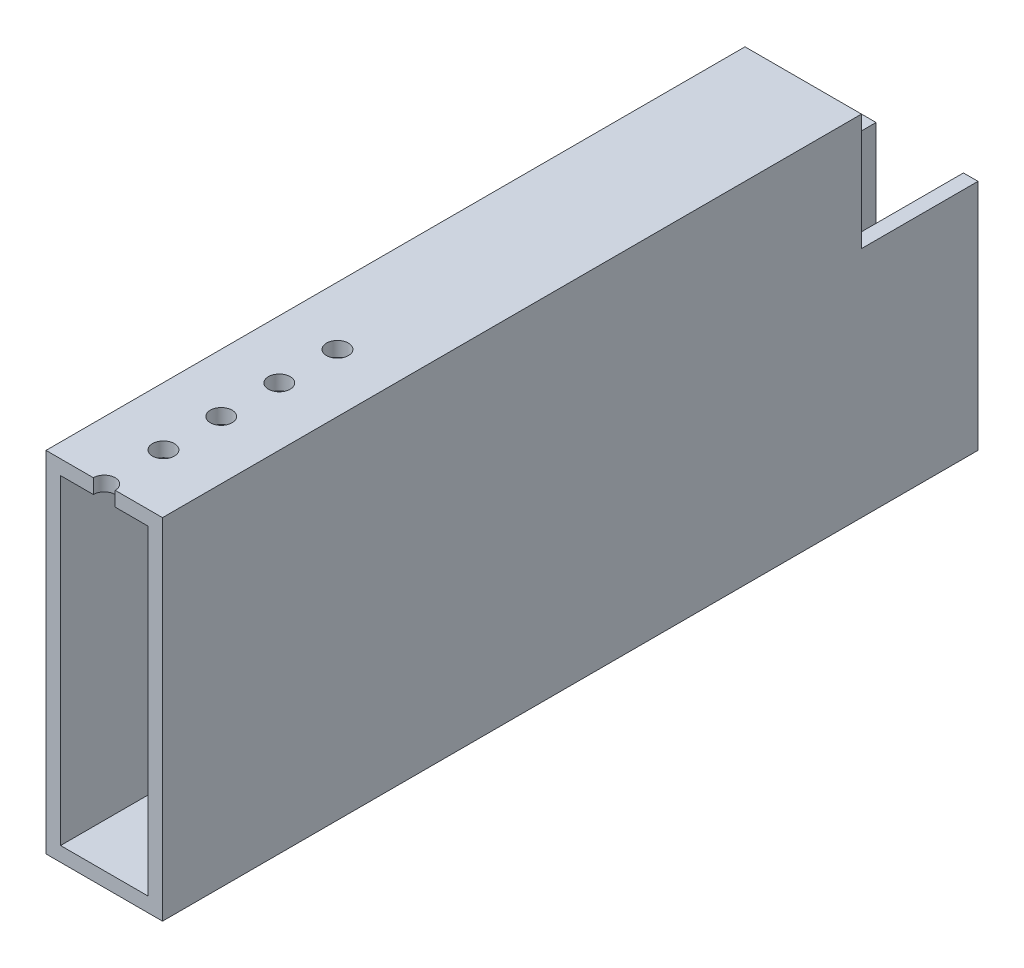
SolidWorks part; units mm, degrees
ref_plane "Front Plane" through (0, 0, 0) normal (0, 0, 1) x (1, 0, 0)
ref_plane "Top Plane" through (0, 0, 0) normal (0, 1, 0) x (1, 0, 0)
ref_plane "Right Plane" through (0, 0, 0) normal (1, 0, 0) x (0, 0, -1)
sketch "Sketch1" plane through (0, 0, 0) normal (0, 0, 1) x (1, 0, 0)
  line L1 (-12.7, -38.1) -> (12.7, -38.1)
  line L2 (-12.7, -38.1) -> (-12.7, 38.1)
  line L3 (-12.7, 38.1) -> (12.7, 38.1)
  line L4 (12.7, -38.1) -> (12.7, 38.1)
  line L5 (-12.7, -38.1) -> (12.7, 38.1) construction
  line L6 (-12.7, 38.1) -> (12.7, -38.1) construction
  point P0 (0, 0)
  dimension "D1" = 25.4
  dimension "D2" = 76.2
extrude "Boss-Extrude1" add sketch "Sketch1" along normal mid plane 177.8
shell "Shell1" thickness 3.175 removed face at (0, 0, -88.9) removed face at (0, 0, 88.9)
sketch "Sketch2" plane through (-12.7, 0, 0) normal (-1, 0, 0) x (0, 0, 1)
  line L1 (-88.9, 38.1) -> (-63.5, 38.1)
  line L2 (-88.9, 38.1) -> (-88.9, 12.7)
  line L3 (-88.9, 12.7) -> (-63.5, 12.7)
  line L4 (-63.5, 38.1) -> (-63.5, 12.7)
  dimension "D1" = 25.4
extrude "Cut-Extrude1" cut sketch "Sketch2" against normal through all
sketch "Sketch3" plane through (0, 38.1, 0) normal (0, 1, 0) x (1, 0, 0)
  line L0 (9.525, -88.9) -> (-9.525, -88.9) construction
  line L1 (12.7, -88.9) -> (-12.7, -88.9) construction
  circle A0 centre (0, -88.9) radius 2.3812
  circle A1 centre (0, -75.9959) radius 2.3812
  circle A2 centre (0, -63.3973) radius 2.3812
  circle A3 centre (0, -50.7315) radius 2.3812
  circle A4 centre (0, -38.0486) radius 2.3812
  point P10 (0, -88.9)
  dimension "D1" = 4.7625
  dimension "D3" = 12.9041
  dimension "D2" = 0
  dimension "D4" = 25.5027
  dimension "D5" = 38.1685
  dimension "D6" = 50.8514
extrude "Cut-Extrude2" cut sketch "Sketch3" against normal up to next
